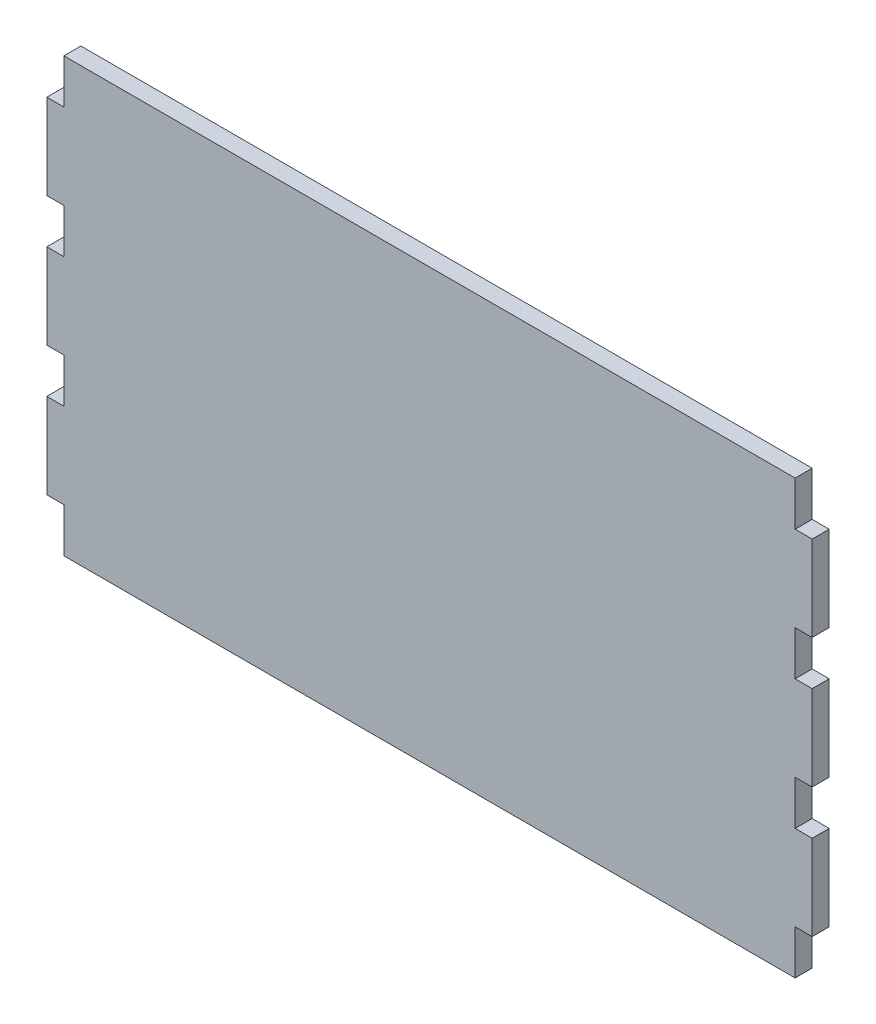
SolidWorks part; units mm, degrees
material "ENPH 253 Hardboard"
ref_plane "Front Plane" through (0, 0, 0) normal (0, 0, 1) x (1, 0, 0)
ref_plane "Top Plane" through (0, 0, 0) normal (0, 1, 0) x (1, 0, 0)
ref_plane "Right Plane" through (0, 0, 0) normal (1, 0, 0) x (0, 0, -1)
sketch "Sketch1" plane through (0, 0, 0) normal (0, 0, 1) x (1, 0, 0)
  line L1 (-67.35, 38.1) -> (67.35, 38.1)
  line L2 (-67.35, 38.1) -> (-67.35, -38.1)
  line L3 (-67.35, -38.1) -> (67.35, -38.1)
  line L4 (67.35, 38.1) -> (67.35, -38.1)
  line L5 (-67.35, 38.1) -> (67.35, -38.1) construction
  line L6 (-67.35, -38.1) -> (67.35, 38.1) construction
  point P0 (0, 0)
  dimension "D1" = 134.7
  dimension "D2" = 76.2
extrude "Boss-Extrude1" add sketch "Sketch1" along normal blind 3
sketch "Sketch2" plane through (0, 0, 3) normal (0, 0, 1) x (1, 0, 0)
  line L1 (-67.35, 38.1) -> (-64.35, 38.1)
  line L2 (-67.35, 38.1) -> (-67.35, 30.3)
  line L3 (-67.35, 30.3) -> (-64.35, 30.3)
  line L4 (-64.35, 38.1) -> (-64.35, 30.3)
  dimension "D1" = 3
  dimension "D2" = 7.8
extrude "Cut-Extrude1" cut sketch "Sketch2" against normal through all
pattern_linear "LPattern1" count 4 spacing 22.8 along (0, -1, 0) of "Cut-Extrude1"
mirror "Mirror4" about plane through (0, 0, 0) normal (1, 0, 0) of "LPattern1"
